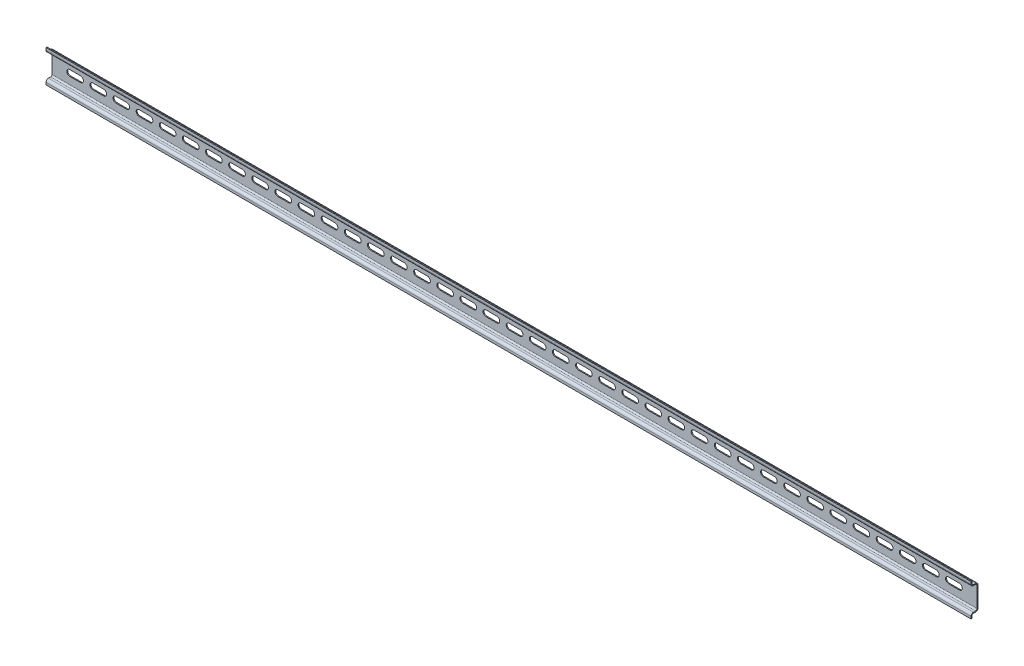
SolidWorks part; units mm, degrees
ref_plane "Front Plane" through (0, 0, 0) normal (0, 0, 1) x (1, 0, 0)
ref_plane "Top Plane" through (0, 0, 0) normal (0, 1, 0) x (1, 0, 0)
ref_plane "Right Plane" through (0, 0, 0) normal (1, 0, 0) x (0, 0, -1)
sketch "Sketch1" plane through (0, 0, 0) normal (1, 0, 0) x (0, 0, -1)
  line L0 (0, 0) -> (96.2341, 0) construction
  line L1 (0, 12.446) -> (0, -12.446)
  line L2 (0, -12.446) -> (-6.484, -12.446)
  line L3 (-6.484, -12.446) -> (-6.484, -17.526)
  line L4 (-6.484, -17.526) -> (-5.484, -17.526)
  line L5 (-5.484, -17.526) -> (-5.484, -13.462)
  line L6 (-5.484, -13.462) -> (1.016, -13.462)
  line L9 (1.016, -13.462) -> (1.016, 13.462)
  line L10 (-5.484, 17.526) -> (-5.484, 13.462)
  line L11 (-6.484, 17.526) -> (-5.484, 17.526)
  line L12 (-6.484, 12.446) -> (-6.484, 17.526)
  line L13 (0, 12.446) -> (-6.484, 12.446)
  line L14 (-5.484, 13.462) -> (1.016, 13.462)
  point P20 (1.016, 0)
  dimension "D1" = 96.2341
  dimension "D2" = 26.924
  dimension "D3" = 7.5
  dimension "D4" = 1
  dimension "D5" = 1.016
  dimension "D8" = 1.016
  dimension "D9" = 35.052
extrude "Boss-Extrude1" add sketch "Sketch1" along normal blind 1000
sketch "Sketch2" plane through (0, 0, -1.016) normal (0, 0, -1) x (-1, 0, 0)
  line L0 (-980.825, 0) -> (-969.175, 0) construction
  line L1 (-980.825, 3.175) -> (-969.175, 3.175)
  line L2 (-980.825, -3.175) -> (-969.175, -3.175)
  line L3 (-1000, -13.462) -> (-1000, 13.462) construction
  line L4 (-955.825, 0) -> (-944.175, 0) construction
  line L5 (-955.825, 3.175) -> (-944.175, 3.175)
  line L6 (-955.825, -3.175) -> (-944.175, -3.175)
  line L7 (-930.825, 0) -> (-919.175, 0) construction
  line L8 (-930.825, 3.175) -> (-919.175, 3.175)
  line L9 (-930.825, -3.175) -> (-919.175, -3.175)
  line L10 (-905.825, 0) -> (-894.175, 0) construction
  line L11 (-905.825, 3.175) -> (-894.175, 3.175)
  line L12 (-905.825, -3.175) -> (-894.175, -3.175)
  line L13 (-880.825, 0) -> (-869.175, 0) construction
  line L14 (-880.825, 3.175) -> (-869.175, 3.175)
  line L15 (-880.825, -3.175) -> (-869.175, -3.175)
  line L16 (-855.825, 0) -> (-844.175, 0) construction
  line L17 (-855.825, 3.175) -> (-844.175, 3.175)
  line L18 (-855.825, -3.175) -> (-844.175, -3.175)
  line L19 (-830.825, 0) -> (-819.175, 0) construction
  line L20 (-830.825, 3.175) -> (-819.175, 3.175)
  line L21 (-830.825, -3.175) -> (-819.175, -3.175)
  line L22 (-805.825, 0) -> (-794.175, 0) construction
  line L23 (-805.825, 3.175) -> (-794.175, 3.175)
  line L24 (-805.825, -3.175) -> (-794.175, -3.175)
  line L25 (-780.825, 0) -> (-769.175, 0) construction
  line L26 (-780.825, 3.175) -> (-769.175, 3.175)
  line L27 (-780.825, -3.175) -> (-769.175, -3.175)
  line L28 (-755.825, 0) -> (-744.175, 0) construction
  line L29 (-755.825, 3.175) -> (-744.175, 3.175)
  line L30 (-755.825, -3.175) -> (-744.175, -3.175)
  line L31 (-730.825, 0) -> (-719.175, 0) construction
  line L32 (-730.825, 3.175) -> (-719.175, 3.175)
  line L33 (-730.825, -3.175) -> (-719.175, -3.175)
  line L34 (-705.825, 0) -> (-694.175, 0) construction
  line L35 (-705.825, 3.175) -> (-694.175, 3.175)
  line L36 (-705.825, -3.175) -> (-694.175, -3.175)
  line L37 (-680.825, 0) -> (-669.175, 0) construction
  line L38 (-680.825, 3.175) -> (-669.175, 3.175)
  line L39 (-680.825, -3.175) -> (-669.175, -3.175)
  line L40 (-655.825, 0) -> (-644.175, 0) construction
  line L41 (-655.825, 3.175) -> (-644.175, 3.175)
  line L42 (-655.825, -3.175) -> (-644.175, -3.175)
  line L44 (-630.825, 0) -> (-619.175, 0) construction
  line L45 (-630.825, 3.175) -> (-619.175, 3.175)
  line L46 (-630.825, -3.175) -> (-619.175, -3.175)
  line L47 (-605.825, 0) -> (-594.175, 0) construction
  line L48 (-605.825, 3.175) -> (-594.175, 3.175)
  line L49 (-605.825, -3.175) -> (-594.175, -3.175)
  line L50 (-580.825, 0) -> (-569.175, 0) construction
  line L51 (-580.825, 3.175) -> (-569.175, 3.175)
  line L52 (-580.825, -3.175) -> (-569.175, -3.175)
  line L53 (-555.825, 0) -> (-544.175, 0) construction
  line L54 (-555.825, 3.175) -> (-544.175, 3.175)
  line L55 (-555.825, -3.175) -> (-544.175, -3.175)
  line L56 (-530.825, 0) -> (-519.175, 0) construction
  line L57 (-530.825, 3.175) -> (-519.175, 3.175)
  line L58 (-530.825, -3.175) -> (-519.175, -3.175)
  line L59 (-505.825, 0) -> (-494.175, 0) construction
  line L60 (-505.825, 3.175) -> (-494.175, 3.175)
  line L61 (-505.825, -3.175) -> (-494.175, -3.175)
  line L62 (-480.825, 0) -> (-469.175, 0) construction
  line L63 (-480.825, 3.175) -> (-469.175, 3.175)
  line L64 (-480.825, -3.175) -> (-469.175, -3.175)
  line L65 (-455.825, 0) -> (-444.175, 0) construction
  line L66 (-455.825, 3.175) -> (-444.175, 3.175)
  line L67 (-455.825, -3.175) -> (-444.175, -3.175)
  line L68 (-430.825, 0) -> (-419.175, 0) construction
  line L69 (-430.825, 3.175) -> (-419.175, 3.175)
  line L70 (-430.825, -3.175) -> (-419.175, -3.175)
  line L71 (-405.825, 0) -> (-394.175, 0) construction
  line L72 (-405.825, 3.175) -> (-394.175, 3.175)
  line L73 (-405.825, -3.175) -> (-394.175, -3.175)
  line L74 (-380.825, 0) -> (-369.175, 0) construction
  line L75 (-380.825, 3.175) -> (-369.175, 3.175)
  line L76 (-380.825, -3.175) -> (-369.175, -3.175)
  line L77 (-355.825, 0) -> (-344.175, 0) construction
  line L78 (-355.825, 3.175) -> (-344.175, 3.175)
  line L79 (-355.825, -3.175) -> (-344.175, -3.175)
  line L80 (-330.825, 0) -> (-319.175, 0) construction
  line L81 (-330.825, 3.175) -> (-319.175, 3.175)
  line L82 (-330.825, -3.175) -> (-319.175, -3.175)
  line L83 (-305.825, 0) -> (-294.175, 0) construction
  line L84 (-305.825, 3.175) -> (-294.175, 3.175)
  line L85 (-305.825, -3.175) -> (-294.175, -3.175)
  line L86 (-280.825, 0) -> (-269.175, 0) construction
  line L87 (-280.825, 3.175) -> (-269.175, 3.175)
  line L88 (-280.825, -3.175) -> (-269.175, -3.175)
  line L89 (-255.825, 0) -> (-244.175, 0) construction
  line L90 (-255.825, 3.175) -> (-244.175, 3.175)
  line L91 (-255.825, -3.175) -> (-244.175, -3.175)
  line L92 (-230.825, 0) -> (-219.175, 0) construction
  line L93 (-230.825, 3.175) -> (-219.175, 3.175)
  line L94 (-230.825, -3.175) -> (-219.175, -3.175)
  line L95 (-205.825, 0) -> (-194.175, 0) construction
  line L96 (-205.825, 3.175) -> (-194.175, 3.175)
  line L97 (-205.825, -3.175) -> (-194.175, -3.175)
  line L98 (-180.825, 0) -> (-169.175, 0) construction
  line L99 (-180.825, 3.175) -> (-169.175, 3.175)
  line L100 (-180.825, -3.175) -> (-169.175, -3.175)
  line L101 (-155.825, 0) -> (-144.175, 0) construction
  line L102 (-155.825, 3.175) -> (-144.175, 3.175)
  line L103 (-155.825, -3.175) -> (-144.175, -3.175)
  line L104 (-130.825, 0) -> (-119.175, 0) construction
  line L105 (-130.825, 3.175) -> (-119.175, 3.175)
  line L106 (-130.825, -3.175) -> (-119.175, -3.175)
  line L107 (-105.825, 0) -> (-94.175, 0) construction
  line L108 (-105.825, 3.175) -> (-94.175, 3.175)
  line L109 (-105.825, -3.175) -> (-94.175, -3.175)
  line L110 (-80.825, 0) -> (-69.175, 0) construction
  line L111 (-80.825, 3.175) -> (-69.175, 3.175)
  line L112 (-80.825, -3.175) -> (-69.175, -3.175)
  line L113 (-55.825, 0) -> (-44.175, 0) construction
  line L114 (-55.825, 3.175) -> (-44.175, 3.175)
  line L115 (-55.825, -3.175) -> (-44.175, -3.175)
  line L116 (-30.825, 0) -> (-19.175, 0) construction
  line L117 (-30.825, 3.175) -> (-19.175, 3.175)
  line L118 (-30.825, -3.175) -> (-19.175, -3.175)
  arc A0 (-980.825, 3.175) -> (-980.825, -3.175) centre (-980.825, 0) ccw
  arc A1 (-969.175, -3.175) -> (-969.175, 3.175) centre (-969.175, 0) ccw
  arc A2 (-955.825, 3.175) -> (-955.825, -3.175) centre (-955.825, 0) ccw
  arc A3 (-944.175, -3.175) -> (-944.175, 3.175) centre (-944.175, 0) ccw
  arc A4 (-930.825, 3.175) -> (-930.825, -3.175) centre (-930.825, 0) ccw
  arc A5 (-919.175, -3.175) -> (-919.175, 3.175) centre (-919.175, 0) ccw
  arc A6 (-905.825, 3.175) -> (-905.825, -3.175) centre (-905.825, 0) ccw
  arc A7 (-894.175, -3.175) -> (-894.175, 3.175) centre (-894.175, 0) ccw
  arc A8 (-880.825, 3.175) -> (-880.825, -3.175) centre (-880.825, 0) ccw
  arc A9 (-869.175, -3.175) -> (-869.175, 3.175) centre (-869.175, 0) ccw
  arc A10 (-855.825, 3.175) -> (-855.825, -3.175) centre (-855.825, 0) ccw
  arc A11 (-844.175, -3.175) -> (-844.175, 3.175) centre (-844.175, 0) ccw
  arc A12 (-830.825, 3.175) -> (-830.825, -3.175) centre (-830.825, 0) ccw
  arc A13 (-819.175, -3.175) -> (-819.175, 3.175) centre (-819.175, 0) ccw
  arc A14 (-805.825, 3.175) -> (-805.825, -3.175) centre (-805.825, 0) ccw
  arc A15 (-794.175, -3.175) -> (-794.175, 3.175) centre (-794.175, 0) ccw
  arc A16 (-780.825, 3.175) -> (-780.825, -3.175) centre (-780.825, 0) ccw
  arc A17 (-769.175, -3.175) -> (-769.175, 3.175) centre (-769.175, 0) ccw
  arc A18 (-755.825, 3.175) -> (-755.825, -3.175) centre (-755.825, 0) ccw
  arc A19 (-744.175, -3.175) -> (-744.175, 3.175) centre (-744.175, 0) ccw
  arc A20 (-730.825, 3.175) -> (-730.825, -3.175) centre (-730.825, 0) ccw
  arc A21 (-719.175, -3.175) -> (-719.175, 3.175) centre (-719.175, 0) ccw
  arc A22 (-705.825, 3.175) -> (-705.825, -3.175) centre (-705.825, 0) ccw
  arc A23 (-694.175, -3.175) -> (-694.175, 3.175) centre (-694.175, 0) ccw
  arc A24 (-680.825, 3.175) -> (-680.825, -3.175) centre (-680.825, 0) ccw
  arc A25 (-669.175, -3.175) -> (-669.175, 3.175) centre (-669.175, 0) ccw
  arc A26 (-655.825, 3.175) -> (-655.825, -3.175) centre (-655.825, 0) ccw
  arc A27 (-644.175, -3.175) -> (-644.175, 3.175) centre (-644.175, 0) ccw
  arc A28 (-630.825, 3.175) -> (-630.825, -3.175) centre (-630.825, 0) ccw
  arc A29 (-619.175, -3.175) -> (-619.175, 3.175) centre (-619.175, 0) ccw
  arc A30 (-605.825, 3.175) -> (-605.825, -3.175) centre (-605.825, 0) ccw
  arc A31 (-594.175, -3.175) -> (-594.175, 3.175) centre (-594.175, 0) ccw
  arc A32 (-580.825, 3.175) -> (-580.825, -3.175) centre (-580.825, 0) ccw
  arc A33 (-569.175, -3.175) -> (-569.175, 3.175) centre (-569.175, 0) ccw
  arc A34 (-555.825, 3.175) -> (-555.825, -3.175) centre (-555.825, 0) ccw
  arc A35 (-544.175, -3.175) -> (-544.175, 3.175) centre (-544.175, 0) ccw
  arc A36 (-530.825, 3.175) -> (-530.825, -3.175) centre (-530.825, 0) ccw
  arc A37 (-519.175, -3.175) -> (-519.175, 3.175) centre (-519.175, 0) ccw
  arc A38 (-505.825, 3.175) -> (-505.825, -3.175) centre (-505.825, 0) ccw
  arc A39 (-494.175, -3.175) -> (-494.175, 3.175) centre (-494.175, 0) ccw
  arc A40 (-480.825, 3.175) -> (-480.825, -3.175) centre (-480.825, 0) ccw
  arc A41 (-469.175, -3.175) -> (-469.175, 3.175) centre (-469.175, 0) ccw
  arc A42 (-455.825, 3.175) -> (-455.825, -3.175) centre (-455.825, 0) ccw
  arc A43 (-444.175, -3.175) -> (-444.175, 3.175) centre (-444.175, 0) ccw
  arc A44 (-430.825, 3.175) -> (-430.825, -3.175) centre (-430.825, 0) ccw
  arc A45 (-419.175, -3.175) -> (-419.175, 3.175) centre (-419.175, 0) ccw
  arc A46 (-405.825, 3.175) -> (-405.825, -3.175) centre (-405.825, 0) ccw
  arc A47 (-394.175, -3.175) -> (-394.175, 3.175) centre (-394.175, 0) ccw
  arc A48 (-380.825, 3.175) -> (-380.825, -3.175) centre (-380.825, 0) ccw
  arc A49 (-369.175, -3.175) -> (-369.175, 3.175) centre (-369.175, 0) ccw
  arc A50 (-355.825, 3.175) -> (-355.825, -3.175) centre (-355.825, 0) ccw
  arc A51 (-344.175, -3.175) -> (-344.175, 3.175) centre (-344.175, 0) ccw
  arc A52 (-330.825, 3.175) -> (-330.825, -3.175) centre (-330.825, 0) ccw
  arc A53 (-319.175, -3.175) -> (-319.175, 3.175) centre (-319.175, 0) ccw
  arc A54 (-305.825, 3.175) -> (-305.825, -3.175) centre (-305.825, 0) ccw
  arc A55 (-294.175, -3.175) -> (-294.175, 3.175) centre (-294.175, 0) ccw
  arc A56 (-280.825, 3.175) -> (-280.825, -3.175) centre (-280.825, 0) ccw
  arc A57 (-269.175, -3.175) -> (-269.175, 3.175) centre (-269.175, 0) ccw
  arc A58 (-255.825, 3.175) -> (-255.825, -3.175) centre (-255.825, 0) ccw
  arc A59 (-244.175, -3.175) -> (-244.175, 3.175) centre (-244.175, 0) ccw
  arc A60 (-230.825, 3.175) -> (-230.825, -3.175) centre (-230.825, 0) ccw
  arc A61 (-219.175, -3.175) -> (-219.175, 3.175) centre (-219.175, 0) ccw
  arc A62 (-205.825, 3.175) -> (-205.825, -3.175) centre (-205.825, 0) ccw
  arc A63 (-194.175, -3.175) -> (-194.175, 3.175) centre (-194.175, 0) ccw
  arc A64 (-180.825, 3.175) -> (-180.825, -3.175) centre (-180.825, 0) ccw
  arc A65 (-169.175, -3.175) -> (-169.175, 3.175) centre (-169.175, 0) ccw
  arc A66 (-155.825, 3.175) -> (-155.825, -3.175) centre (-155.825, 0) ccw
  arc A67 (-144.175, -3.175) -> (-144.175, 3.175) centre (-144.175, 0) ccw
  arc A68 (-130.825, 3.175) -> (-130.825, -3.175) centre (-130.825, 0) ccw
  arc A69 (-119.175, -3.175) -> (-119.175, 3.175) centre (-119.175, 0) ccw
  arc A70 (-105.825, 3.175) -> (-105.825, -3.175) centre (-105.825, 0) ccw
  arc A71 (-94.175, -3.175) -> (-94.175, 3.175) centre (-94.175, 0) ccw
  arc A72 (-80.825, 3.175) -> (-80.825, -3.175) centre (-80.825, 0) ccw
  arc A73 (-69.175, -3.175) -> (-69.175, 3.175) centre (-69.175, 0) ccw
  arc A74 (-55.825, 3.175) -> (-55.825, -3.175) centre (-55.825, 0) ccw
  arc A75 (-44.175, -3.175) -> (-44.175, 3.175) centre (-44.175, 0) ccw
  arc A76 (-30.825, 3.175) -> (-30.825, -3.175) centre (-30.825, 0) ccw
  arc A77 (-19.175, -3.175) -> (-19.175, 3.175) centre (-19.175, 0) ccw
  point P3 (-975, 0)
  point P8 (-984, 0)
  point P9 (-966, 0)
  point P15 (-950, 0)
  point P22 (-925, 0)
  point P29 (-900, 0)
  point P36 (-875, 0)
  point P43 (-850, 0)
  point P50 (-825, 0)
  point P57 (-800, 0)
  point P64 (-775, 0)
  point P71 (-750, 0)
  point P78 (-725, 0)
  point P85 (-700, 0)
  point P92 (-675, 0)
  point P99 (-650, 0)
  point P107 (-625, 0)
  point P114 (-600, 0)
  point P121 (-575, 0)
  point P128 (-550, 0)
  point P135 (-525, 0)
  point P142 (-500, 0)
  point P149 (-475, 0)
  point P156 (-450, 0)
  point P163 (-425, 0)
  point P170 (-400, 0)
  point P177 (-375, 0)
  point P184 (-350, 0)
  point P191 (-325, 0)
  point P198 (-300, 0)
  point P205 (-275, 0)
  point P212 (-250, 0)
  point P219 (-225, 0)
  point P226 (-200, 0)
  point P233 (-175, 0)
  point P240 (-150, 0)
  point P247 (-125, 0)
  point P254 (-100, 0)
  point P261 (-75, 0)
  point P268 (-50, 0)
  point P274 (-25, 0)
  dimension "D1" = 3.175
  dimension "D2" = 18
  dimension "D3" = 25
  dimension "D4" = 39
extrude "Cut-Extrude1" cut sketch "Sketch2" against normal through all
fillet "Fillet1" radius 2.54 4 edges at (500, -12.446, 6.484) (500, 12.446, 6.484) (500, -13.462, -1.016) (500, 13.462, -1.016)
fillet "Fillet2" radius 1.524 4 edges at (500, -13.462, 5.484) (500, 12.446, 0) (500, -12.446, 0) (500, 13.462, 5.484)
